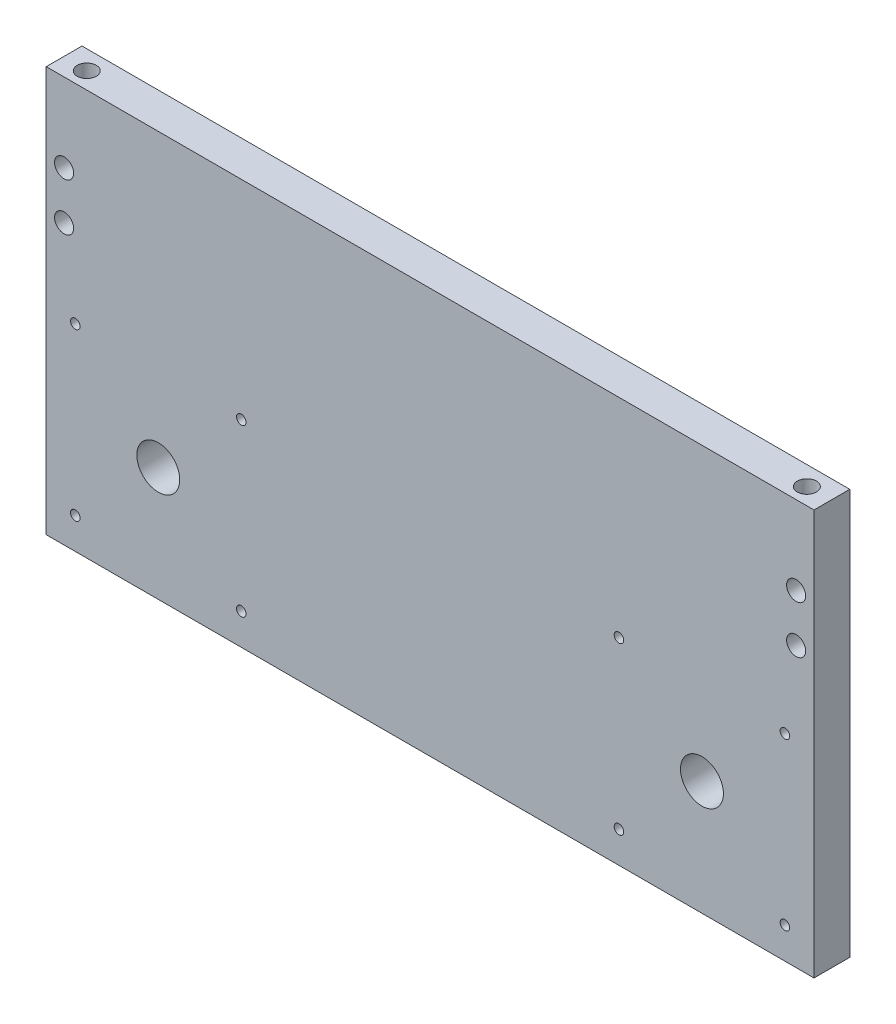
SolidWorks part; units mm, degrees
ref_plane "Płaszczyzna przednia" through (0, 0, 0) normal (0, 0, 1) x (1, 0, 0)
ref_plane "Płaszczyzna górna" through (0, 0, 0) normal (0, 1, 0) x (1, 0, 0)
ref_plane "Płaszczyzna prawa" through (0, 0, 0) normal (1, 0, 0) x (0, 0, -1)
sketch "Szkic1" plane through (0, 0, 0) normal (0, 0, 1) x (1, 0, 0)
  line L1 (161, -85) -> (-161, -85)
  line L2 (161, -85) -> (161, 85)
  line L3 (161, 85) -> (-161, 85)
  line L4 (-161, -85) -> (-161, 85)
  line L5 (161, -85) -> (-161, 85) construction
  line L6 (161, 85) -> (-161, -85) construction
  point P0 (0, 0)
  dimension "D1" = 322
  dimension "D2" = 170
extrude "Dodanie-wyciągnięcie1" add sketch "Szkic1" along normal blind 15
sketch "Szkic2" plane through (0, 0, 15) normal (0, 0, 1) x (1, 0, 0)
  line L2 (-161, -85) -> (161, -85) construction
  line L7 (-161, 85) -> (-161, -85) construction
  circle A1 centre (-148.8, -71.87) radius 2
  dimension "D1" = 13.13
  dimension "D2" = 12.2
  dimension "D5" = 4
extrude "Wytnij-wyciągnięcie2" cut sketch "Szkic2" against normal blind 17.75 contours A1 region at (-148.8, -71.87, 15)
pattern_linear "Szyk liniowy1" count 2 spacing 69.6 along (1, 0, 0) count 2 spacing 69.6 along (0, 1, 0) of "Wytnij-wyciągnięcie2"
sketch "Szkic5" plane through (0, 0, 0) normal (0, 0, -1) x (-1, 0, 0)
  line L1 (161, -85) -> (-161, -85) construction
  line L2 (161, 85) -> (161, -85) construction
  circle A1 centre (114, -37.07) radius 37.5
  dimension "D1" = 47.93
  dimension "D5" = 75
  dimension "D2" = 47
extrude "Wytnij-wyciągnięcie3" cut sketch "Szkic5" against normal blind 2 contours A1 region at (-114, -37.07, 0)
sketch "Szkic7" plane through (0, 0, 2) normal (0, 0, -1) x (-1, 0, 0)
  circle A3 centre (114, -37.07) radius 9
  dimension "D1" = 18
extrude "Wytnij-wyciągnięcie4" cut sketch "Szkic7" against normal blind 17.75 contours A3 region at (-114, -37.07, 2)
pattern_linear "Szyk liniowy2" count 2 spacing 228 along (1, 0, 0) of "Wytnij-wyciągnięcie2", "Szyk liniowy1", "Wytnij-wyciągnięcie3", "Wytnij-wyciągnięcie4"
sketch "Szkic8" plane through (0, 85, 0) normal (0, 1, 0) x (1, 0, 0)
  line L0 (-161, -15) -> (-161, 0) construction
  line L1 (161, -15) -> (-161, -15) construction
  line L2 (161, -15) -> (161, 0) construction
  line L3 (161, -15) -> (-161, -15) construction
  circle A0 centre (-151, -8) radius 4
  circle A1 centre (151, -8) radius 4
  dimension "D1" = 10
  dimension "D3" = 8
  dimension "D6" = 8
  dimension "D2" = 7
  dimension "D4" = 10
  dimension "D5" = 7
extrude "Wytnij-wyciągnięcie5" cut sketch "Szkic8" against normal blind 20
sketch "Szkic10" plane through (0, 0, 15) normal (0, 0, 1) x (1, 0, 0)
  line L0 (161, 85) -> (-161, 85) construction
  line L1 (-161, 85) -> (-161, -85) construction
  circle A0 centre (-153.5, 52) radius 4
  circle A1 centre (-153.5, 32) radius 4
  dimension "D1" = 53
  dimension "D3" = 8
  dimension "D4" = 8
  dimension "D2" = 20
  dimension "D5" = 7.5
extrude "Wytnij-wyciągnięcie7" cut sketch "Szkic10" against normal through all
sketch "Szkic11" plane through (0, 0, 15) normal (0, 0, 1) x (1, 0, 0)
  line L0 (161, 85) -> (-161, 85) construction
  line L1 (161, -85) -> (161, 85) construction
  circle A0 centre (153.5, 32) radius 4
  circle A1 centre (153.5, 52) radius 4
  dimension "D1" = 53
  dimension "D2" = 8
  dimension "D3" = 8
  dimension "D4" = 7.5
  dimension "D5" = 20
extrude "Wytnij-wyciągnięcie8" cut sketch "Szkic11" against normal through all
